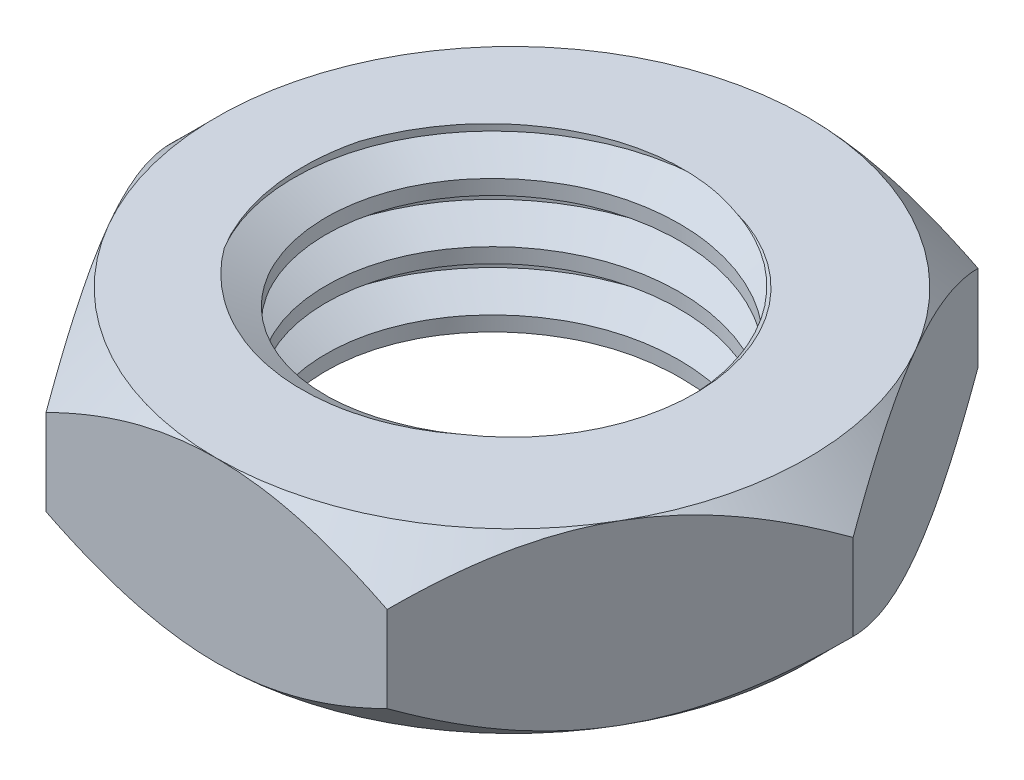
SolidWorks part; units mm, degrees
ref_plane "Front Plane" through (0, 0, 0) normal (0, 0, 1) x (1, 0, 0)
ref_plane "Top Plane" through (0, 0, 0) normal (0, 1, 0) x (1, 0, 0)
ref_plane "Right Plane" through (0, 0, 0) normal (1, 0, 0) x (0, 0, -1)
sketch "Sketch1" plane through (0, 0, 0) normal (0, 1, 0) x (1, 0, 0)
  line L1 (2.8868, 0) -> (1.4434, 2.5)
  line L2 (1.4434, 2.5) -> (-1.4434, 2.5)
  line L3 (-1.4434, 2.5) -> (-2.8868, 0)
  line L4 (-2.8868, 0) -> (-1.4434, -2.5)
  line L5 (-1.4434, -2.5) -> (1.4434, -2.5)
  line L6 (1.4434, -2.5) -> (2.8868, 0)
  circle A0 centre (0, 0) radius 2.5 construction
  dimension "D1" = 5
extrude "Boss-Extrude1" add sketch "Sketch1" along normal mid plane 1.5
sketch "Sketch2" plane through (0, 0.75, 0) normal (0, 1, 0) x (1, 0, 0)
  line L0 (1.4434, 2.5) -> (-1.4434, 2.5) construction
  circle A0 centre (0, 0) radius 2.5
extrude "Cut-Extrude1" cut sketch "Sketch2" against normal through all draft 45 flip side to cut
mirror "Mirror1" about plane through (0, 0, 0) normal (0, 1, 0) of "Cut-Extrude1"
sketch "Sketch3" plane through (0, 0.75, 0) normal (0, 1, 0) x (1, 0, 0)
  circle A0 centre (0, 0) radius 1.5
  dimension "D1" = 3
extrude "Cut-Extrude2" cut sketch "Sketch3" against normal through all
chamfer "Chamfer1" distance 0.05 angle 45 2 edges at (0, -0.75, 1.5) (0, 0.75, 1.5)
thread "Thread1" pitch 0.5 method cut profile "Thread Profile1" start angle 0, offset 1, length 0, pitch 0.5, diameter 3
ref_plane "Plane1" through (1.5, -1.7, 0) normal (0, 0, 1) x (1, 0, 0)
sketch "Thread Profile1" plane through (1.5, -1.7, 0) normal (0, 0, 1) x (1, 0, 0)
  line L0 (0, 0) -> (0, 0.5) construction
  line L1 (0, 0) -> (0.2706, 0.1562)
  line L2 (0.2706, 0.1562) -> (0.2706, 0.2187)
  line L3 (0.2706, 0.2187) -> (0, 0.375)
  line L4 (0.2706, 0.1875) -> (0, 0.1875) construction
  line L11 (0, 0) -> (0, 0.375)
  point P2 (0, 0)
  dimension "Pitch" = 0.5
  dimension "Profile_Angle" = 60
  dimension "Profile_Land" = 0.0625
  dimension "Profile_Height" = 0.2706
equation "\"Nut Head Dia\"= 5mm"
equation "\"Nut Head Thickness\"= 1.5mm"
equation "\"Nut hole Dia\" = 3mm"
equation "\"D1@Sketch1\"=\"Nut Head Dia\""
equation "\"D1@Boss-Extrude1\"=\"Nut Head Thickness\""
equation "\"D1@Sketch3\"=\"Nut hole Dia\""
